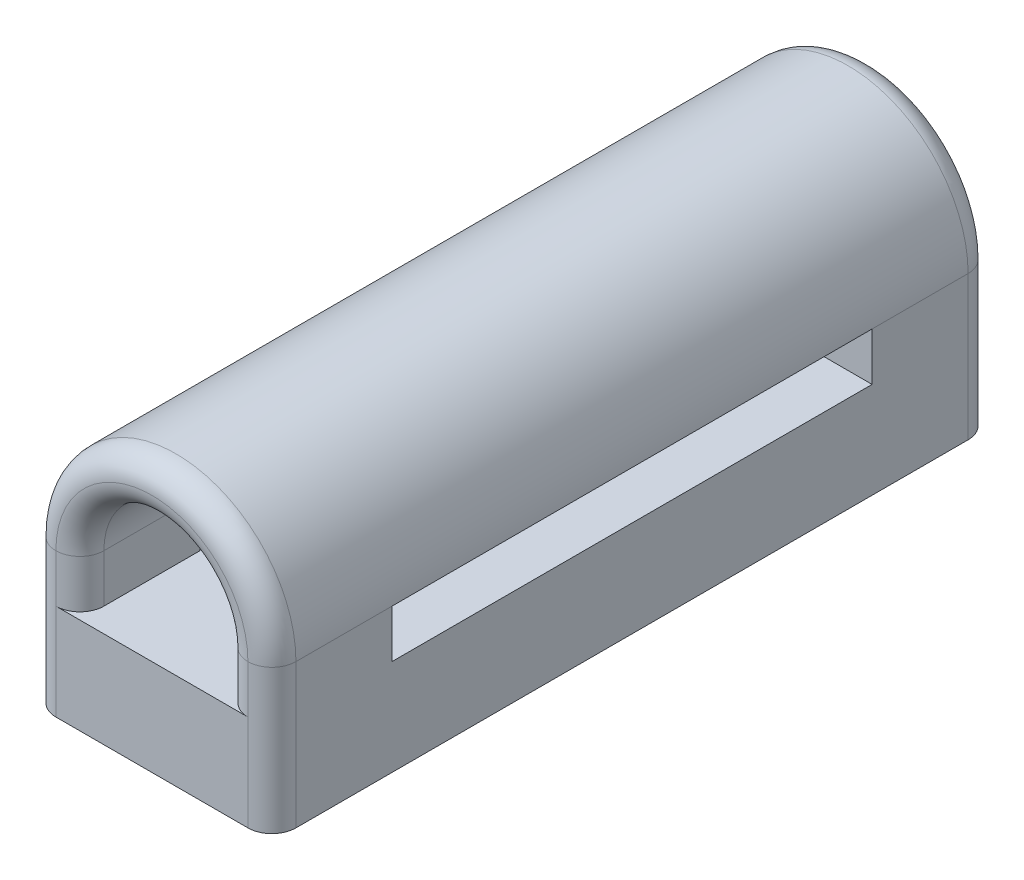
SolidWorks part; units mm, degrees
ref_plane "Płaszczyzna przednia" through (0, 0, 0) normal (0, 0, 1) x (1, 0, 0)
ref_plane "Płaszczyzna górna" through (0, 0, 0) normal (0, 1, 0) x (1, 0, 0)
ref_plane "Płaszczyzna prawa" through (0, 0, 0) normal (1, 0, 0) x (0, 0, -1)
sketch "Szkic1" plane through (0, 0, 0) normal (0, 0, 1) x (1, 0, 0)
  line L0 (-1.5, 0) -> (1.5, 0)
  line L1 (-2.5, 0) -> (-1.5, 0)
  line L2 (1.5, 0) -> (2.5, 0)
  arc A2 (-1.5, 0) -> (1.5, 0) centre (0, 0) cw
  arc A3 (-2.5, 0) -> (2.5, 0) centre (0, 0) cw
  dimension "D1" = 3
  dimension "D2" = 5
extrude "Dodanie-wyciągnięcie2" add sketch "Szkic1" along normal blind 15 contours A3 L1 A2 L2 region at (-2, 0.0559, 0)
sketch "Szkic3" plane through (0, 0, 0) normal (0, -1, 0) x (1, 0, 0)
  line L0 (-1.5, 15) -> (-1.5, 0) construction
  line L1 (-2.5, 15) -> (-1.5, 15)
  line L2 (-2.5, 15) -> (-2.5, 12.5)
  line L3 (-2.5, 12.5) -> (-1.5, 12.5)
  line L4 (-1.5, 15) -> (-1.5, 12.5)
  line L5 (1.5, 15) -> (1.5, 0) construction
  line L6 (2.5, 15) -> (1.5, 15)
  line L7 (2.5, 15) -> (2.5, 12.5)
  line L8 (2.5, 12.5) -> (1.5, 12.5)
  line L9 (1.5, 15) -> (1.5, 12.5)
  line L11 (2.5, 0) -> (1.5, 0)
  line L12 (2.5, 0) -> (2.5, 2.5)
  line L13 (2.5, 2.5) -> (1.5, 2.5)
  line L14 (1.5, 0) -> (1.5, 2.5)
  line L15 (-2.5, 0) -> (-1.5, 0)
  line L16 (-2.5, 0) -> (-2.5, 2.5)
  line L17 (-2.5, 2.5) -> (-1.5, 2.5)
  line L18 (-1.5, 0) -> (-1.5, 2.5)
  dimension "D1" = 10
extrude "Dodanie-wyciągnięcie3" add sketch "Szkic3" along normal blind 3
sketch "Szkic4" plane through (0, 0, 12.5) normal (0, 0, -1) x (-1, 0, 0)
  line L0 (1.5, -3) -> (1.5, 0) construction
  line L1 (2.5, -3) -> (1.5, -3)
  line L2 (2.5, -3) -> (2.5, -1)
  line L3 (2.5, -1) -> (1.5, -1)
  line L4 (1.5, -3) -> (1.5, -1)
  line L5 (-2.5, -3) -> (-2.5, 0) construction
  line L6 (-1.5, -3) -> (-2.5, -3)
  line L7 (-1.5, -3) -> (-1.5, -1)
  line L8 (-1.5, -1) -> (-2.5, -1)
  line L9 (-2.5, -3) -> (-2.5, -1)
  dimension "D1" = 2
extrude "Dodanie-wyciągnięcie4" add sketch "Szkic4" along normal blind 10
sketch "Szkic6" plane through (-1.5, 0, 0) normal (1, 0, 0) x (0, 0, -1)
  line L0 (0, -3) -> (0, 0) construction
  line L1 (-15, -3) -> (0, -3)
  line L2 (-15, -3) -> (-15, -1)
  line L3 (-15, -1) -> (0, -1)
  line L4 (0, -3) -> (0, -1)
  line L5 (-2.5, -1) -> (-12.5, -1) construction
extrude "Dodanie-wyciągnięcie5" add sketch "Szkic6" along normal blind 3
fillet "Zaokrąglenie1" radius 0.5 12 edges at (-1.5, -0.5, 0) (1.5, -0.5, 0) (-1.5, -0.5, 15) (1.5, -0.5, 15) (0, 1.5, 0) (0, 1.5, 15) (2.5, -1.5, 15) (0, 2.5, 15) (2.5, -1.5, 0) (0, 2.5, 0) (-2.5, -1.5, 15) (-2.5, -1.5, 0)
